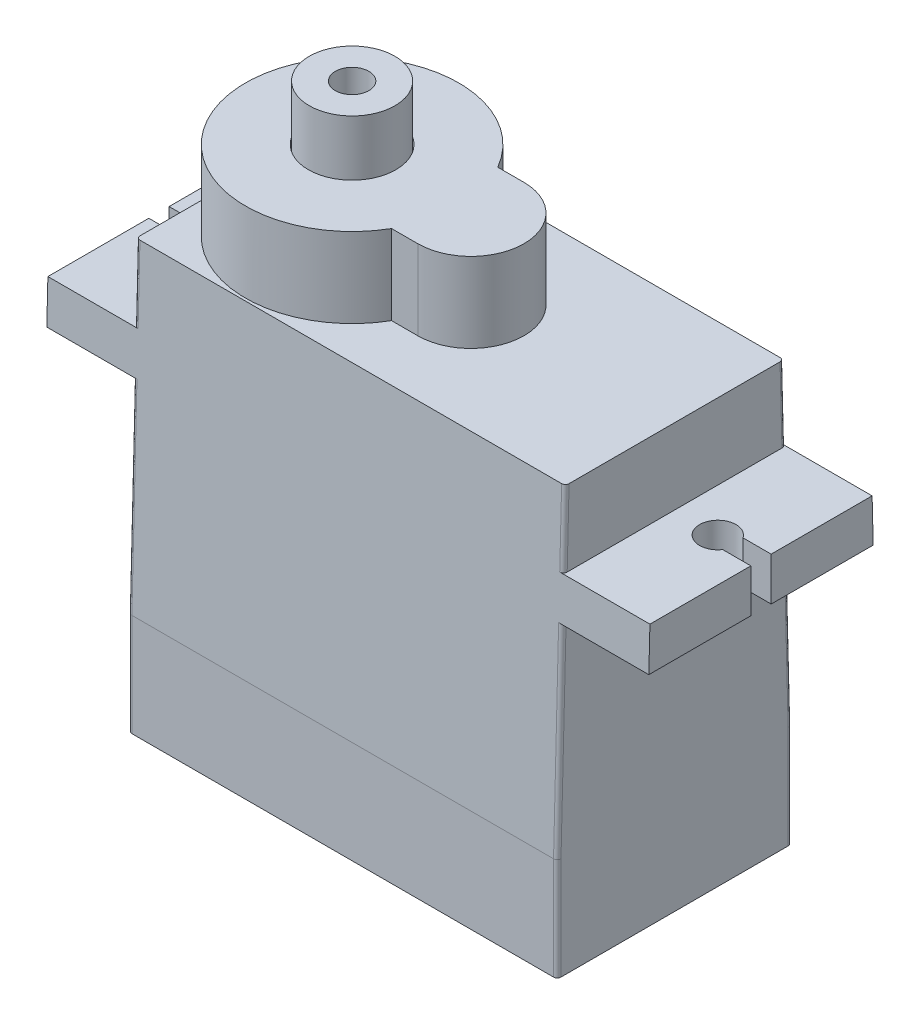
SolidWorks part; units mm, degrees
ref_plane "Front Plane" through (0, 0, 0) normal (0, 0, 1) x (1, 0, 0)
ref_plane "Top Plane" through (0, 0, 0) normal (0, 1, 0) x (1, 0, 0)
ref_plane "Right Plane" through (0, 0, 0) normal (1, 0, 0) x (0, 0, -1)
ref_axis "X-Axis" through (-88.99, 0, 0) along (1, 0, 0)
ref_axis "Y-Axis" through (0, 0, -88.99) along (0, 0, 1)
ref_axis "Z-Axis" through (0, 55, 0) along (0, -1, 0)
sketch "Sketch1" plane through (0, 0, 0) normal (0, 0, 1) x (1, 0, 0)
  line L0 (0, 0) -> (0, 12.96) construction
  line L1 (-7.13, 6.38) -> (15.9, 6.38)
  line L2 (-7.13, 6.38) -> (-7.13, 2.32)
  line L3 (-7.13, -16.34) -> (15.9, -16.34)
  line L4 (15.9, 6.38) -> (15.9, 2.32)
  line L5 (15.9, 2.32) -> (20.54, 2.32)
  line L6 (-11.77, 2.32) -> (-7.13, 2.32)
  line L7 (-11.77, 2.32) -> (-11.77, 0)
  line L8 (-11.77, 0) -> (-7.13, 0)
  line L9 (20.54, 2.32) -> (20.54, 0)
  line L10 (15.9, 0) -> (20.54, 0)
  line L11 (-7.13, 0) -> (-7.13, -16.34)
  line L12 (15.9, 0) -> (15.9, -16.34)
  line L14 (15.9, 0) -> (-7.13, 0) construction
  point P3 (4.385, 0)
  dimension "D1" = 2.32
  dimension "D2" = 32.31
  dimension "D3" = 23.03
  dimension "D4" = 16.34
  dimension "D5" = 22.72
  dimension "D6" = 7.13
  dimension "D7" = 15.9
  dimension "D10" = 29.3
  dimension "D11" = 4.385
extrude "Boss-Extrude1" add sketch "Sketch1" along normal mid plane 12.59
sketch "Sketch2" plane through (0, 6.38, 0) normal (0, 1, 0) x (1, 0, 0)
  line L0 (-1.405, 0) -> (4.97, 0) construction
  line L1 (3.5602, -2.85) -> (4.97, -2.85)
  line L2 (4.97, 2.85) -> (3.5602, 2.85)
  line L3 (-1.405, 0) -> (-7.13, 0) construction
  line L4 (4.97, 0) -> (7.82, 0) construction
  line L5 (-7.13, -6.295) -> (-7.13, 6.295) construction
  arc A0 (3.5602, 2.85) -> (3.5602, -2.85) centre (-1.405, 0) ccw
  arc A1 (4.97, -2.85) -> (4.97, 2.85) centre (4.97, 0) ccw
  dimension "D1" = 11.45
  dimension "D2" = 5.7
  dimension "D3" = 14.95
extrude "Boss-Extrude2" add sketch "Sketch2" along normal blind 4.28
sketch "Sketch11" plane through (-11.77, 0, 0) normal (-1, 0, 0) x (0, 0, 1)
  line L0 (-5.86, 6.38) -> (-6.295, -10.84)
  line L1 (0, 6.38) -> (-6.295, 6.38) construction
  line L2 (6.295, -16.34) -> (-6.295, -16.34) construction
  line L3 (-6.295, 0) -> (-6.295, -16.34) construction
  line L4 (-5.86, 6.38) -> (-6.295, 6.38)
  line L5 (-6.295, 6.38) -> (-6.295, -10.84)
  dimension "D1" = 5.86
  dimension "D2" = 5.5
extrude "Cut-Extrude4" cut sketch "Sketch11" against normal through all
mirror "Mirror1" about plane through (0, 0, 0) normal (0, 0, 1) of "Cut-Extrude4"
sketch "Sketch4" plane through (0, 0, 0) normal (0, 1, 0) x (1, 0, 0)
  line L0 (-7.13, 0) -> (-9.45, 0) construction
  line L1 (-11.77, -5.9626) -> (-11.77, 5.9626) construction
  line L2 (-10.2585, 0.545) -> (-11.77, 0.545)
  line L3 (-10.2585, 0.545) -> (-10.2585, -0.545)
  line L4 (-10.2585, -0.545) -> (-11.77, -0.545)
  line L5 (-11.77, 0.545) -> (-11.77, -0.545)
  line L8 (-9.45, 0) -> (-10.2585, 0) construction
  line L9 (-9.45, 0) -> (-11.77, 0) construction
  arc A0 (3.5602, 2.85) -> (3.5602, -2.85) centre (-1.405, 0) ccw construction
  circle A1 centre (-9.45, 0) radius 0.975
  dimension "D1" = 1.09
  dimension "D2" = 1.95
extrude "Cut-Extrude1" cut sketch "Sketch4" along normal through all contours A1 | L4 L5 L2 L3
sketch "Sketch14" plane through (0, 0.152, 6.0173) normal (0, 0.0253, 0.9997) x (1, 0, 0)
  line L0 (4.385, -10.9955) -> (-7.13, -10.9955) construction
  line L1 (15.9, -10.9955) -> (-7.13, -10.9955) construction
ref_plane "Plane1" through (4.385, -10.84, 6.295) normal (-1, 0, 0) x (0, 0, 1)
mirror "Mirror2" about plane through (4.385, -10.84, 6.295) normal (-1, 0, 0) of "Cut-Extrude1"
sketch "Sketch5" plane through (0, -16.34, 0) normal (0, -1, 0) x (1, 0, 0)
  line L0 (15.9, 6.295) -> (-7.13, -6.295) construction
  line L17 (-5.49, 4.35) -> (14.26, 4.35) construction
  line L18 (-5.49, 4.35) -> (-5.49, -4.35) construction
  line L19 (-5.49, -4.35) -> (14.26, -4.35) construction
  line L20 (14.26, 4.35) -> (14.26, -4.35) construction
  line L21 (-5.49, 4.35) -> (14.26, -4.35) construction
  circle A0 centre (-5.49, 4.35) radius 1
  circle A1 centre (-5.49, -4.35) radius 1
  circle A2 centre (14.26, -4.35) radius 1
  circle A3 centre (14.26, 4.35) radius 1
  circle A4 centre (-5.49, 4.35) radius 0.975
  circle A5 centre (-5.49, -4.35) radius 0.975
  circle A6 centre (14.26, -4.35) radius 0.975
  circle A7 centre (14.26, 4.35) radius 0.975
  point P36 (4.385, 0)
  dimension "D1" = 0.025
  dimension "D4" = 1.95
  dimension "D5" = 19.75
  dimension "D6" = 8.7
extrude "Cut-Extrude2" cut sketch "Sketch5" against normal blind 1
sketch "Sketch6" plane through (-7.13, 0, 0) normal (-1, 0, 0) x (0, 0, 1)
  line L0 (-1.05, -11.34) -> (1.05, -11.34) construction
  line L1 (0, -11.84) -> (0, -16.34) construction
  line L3 (6.295, -16.34) -> (-6.295, -16.34) construction
  circle A0 centre (0, -11.34) radius 0.5
  circle A1 centre (1.05, -11.34) radius 0.5
  circle A2 centre (-1.05, -11.34) radius 0.5
  dimension "D3" = 1
  dimension "D1" = 4.5
  dimension "D2" = 2.1
extrude "Boss-Extrude4" [suppressed] add sketch "Sketch6" along normal blind 8
sketch "Sketch7" [suppressed] plane through (-15.13, 0, 0) normal (-1, 0, 0) x (0, 0, 1)
  circle A0 centre (0, -11.34) radius 0.25
  circle A1 centre (1.05, -11.34) radius 0.25
  circle A2 centre (-1.05, -11.34) radius 0.25
  dimension "D1" = 0.5
extrude "Boss-Extrude5" [suppressed] add sketch "Sketch7" along normal blind 1
sketch "Sketch3" plane through (0, 10.66, 0) normal (0, 1, 0) x (1, 0, 0)
  line L0 (4.7718, -0.52) -> (4.97, -0.52)
  line L1 (4.97, 0.52) -> (4.7718, 0.52)
  line L2 (5.49, 0) -> (7.82, 0) construction
  line L3 (-4.8, 0) -> (-7.13, 0) construction
  arc A0 (4.7718, 0.52) -> (4.7718, -0.52) centre (0, 0) ccw
  arc A1 (4.97, -0.52) -> (4.97, 0.52) centre (4.97, 0) ccw
  arc A2 (4.97, -2.85) -> (4.97, 2.85) centre (4.97, 0) ccw construction
  arc A3 (3.5602, 2.85) -> (3.5602, -2.85) centre (-1.405, 0) ccw construction
  dimension "D1" = 9.6
fillet "Fillet1" radius 0.3 4 edges at (14.26, -16.34, -5.325) (14.26, -16.34, 3.375) (-5.49, -16.34, -5.325) (-5.49, -16.34, 3.375)
fillet "Fillet3" radius 0.2 12 edges at (15.9, -13.59, -6.295) (15.9, -13.59, 6.295) (-7.13, -13.59, -6.295) (-7.13, -13.59, 6.295) (-7.13, -5.42, 6.1581) (-7.13, -5.42, -6.1581) (15.9, -5.42, 6.1581) (15.9, -5.42, -6.1581) (15.9, 4.35, -5.9113) (15.9, 4.35, 5.9113) (-7.13, 4.35, -5.9113) (-7.13, 4.35, 5.9113)
sketch "Sketch12" plane through (0, 10.66, 0) normal (0, 1, 0) x (1, 0, 0)
  circle A0 centre (-1.405, 0) radius 2.3
  circle A1 centre (-1.405, 0) radius 0.9
  dimension "D1" = 4.6
  dimension "D2" = 1.8
extrude "Boss-Extrude6" add sketch "Sketch12" along normal blind 2.95 and the other way blind 1 separate body
sketch "Sketch13" plane through (0, 13.61, 0) normal (0, 1, 0) x (1, 0, 0)
  circle A0 centre (-1.405, 0) radius 2.35
  dimension "D1" = 4.7
extrude "Cut-Extrude5" cut sketch "Sketch13" against normal blind 5
